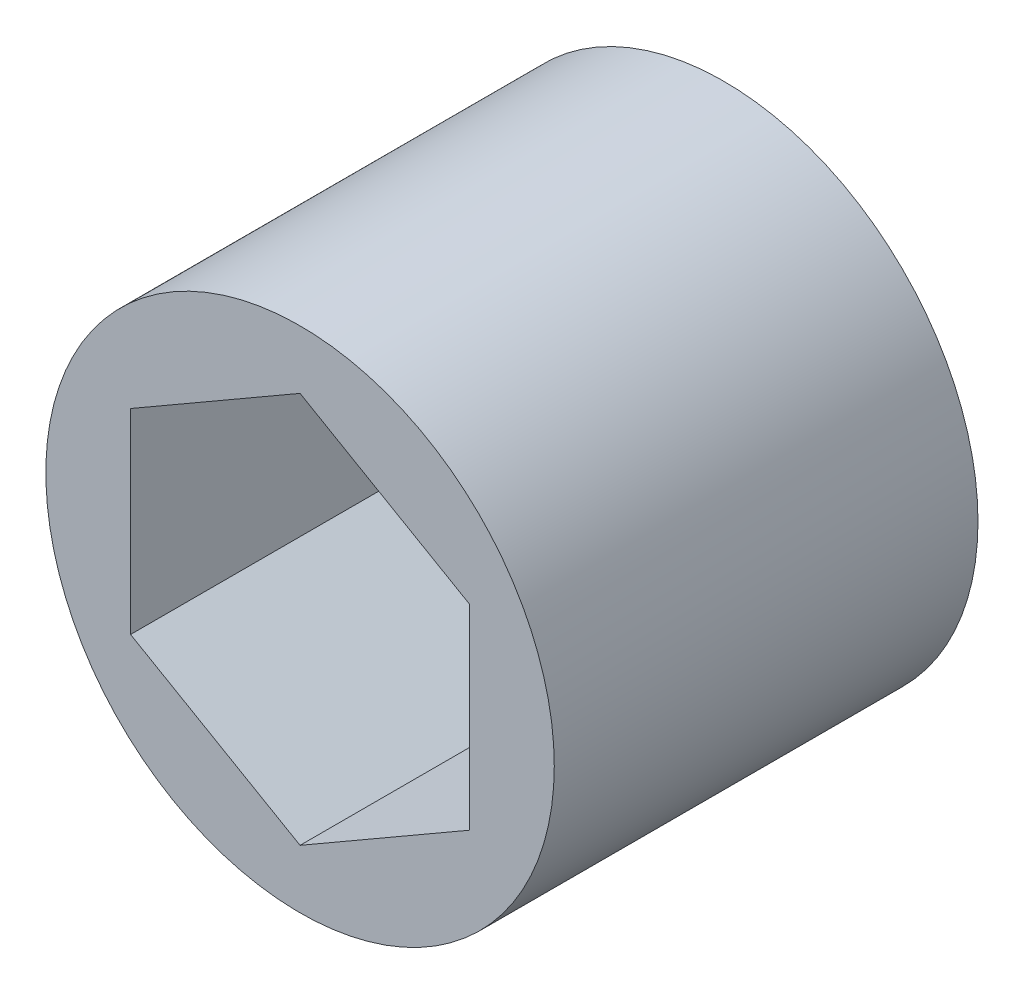
SolidWorks part; units mm, degrees
material "Nylon 101"
ref_plane "Front Plane" through (0, 0, 0) normal (0, 0, 1) x (1, 0, 0)
ref_plane "Top Plane" through (0, 0, 0) normal (0, 1, 0) x (1, 0, 0)
ref_plane "Right Plane" through (0, 0, 0) normal (1, 0, 0) x (0, 0, -1)
sketch "Sketch1" plane through (0, 0, 0) normal (0, 0, 1) x (1, 0, 0)
  line L1 (0, 7.3323) -> (-6.35, 3.6662)
  line L2 (-6.35, 3.6662) -> (-6.35, -3.6662)
  line L3 (-6.35, -3.6662) -> (0, -7.3323)
  line L4 (0, -7.3323) -> (6.35, -3.6662)
  line L5 (6.35, -3.6662) -> (6.35, 3.6662)
  line L6 (6.35, 3.6662) -> (0, 7.3323)
  circle A0 centre (0, 0) radius 6.35 construction
  circle A1 centre (0, 0) radius 9.525
  dimension "D1" = 12.7
  dimension "D2" = 19.05
extrude "Boss-Extrude1" add sketch "Sketch1" along normal blind 15.875
